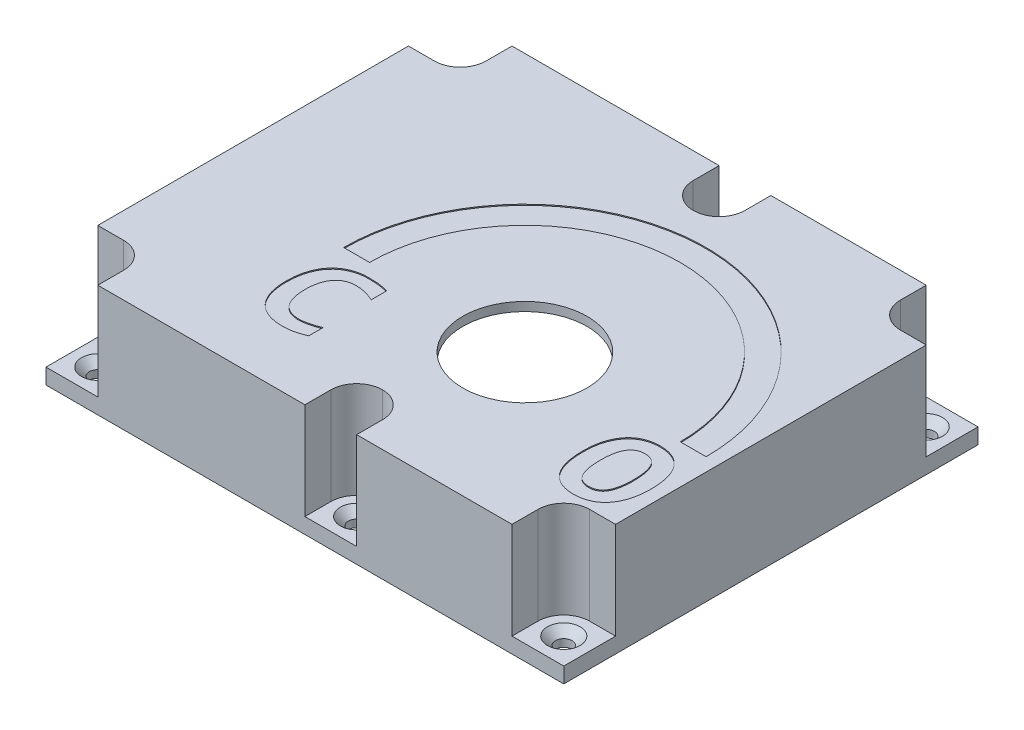
SolidWorks part; units mm, degrees
ref_plane "Płaszczyzna przednia" through (0, 0, 0) normal (0, 0, 1) x (1, 0, 0)
ref_plane "Płaszczyzna górna" through (0, 0, 0) normal (0, 1, 0) x (1, 0, 0)
ref_plane "Płaszczyzna prawa" through (0, 0, 0) normal (1, 0, 0) x (0, 0, -1)
sketch "Sketch1" plane through (0, 0, 0) normal (0, 1, 0) x (1, 0, 0)
  line L0 (-49.242, 28.8418) -> (-44.241, 28.8418)
  line L5 (-49.242, 38.8418) -> (0.758, 38.8418) construction
  line L18 (-49.242, 38.8418) -> (-49.242, -41.1582) construction
  line L19 (-49.242, -41.1582) -> (0.758, -41.1582) construction
  line L21 (50.758, 38.8418) -> (50.758, -41.1582) construction
  line L22 (-49.242, 38.8418) -> (-39.242, 38.8418) construction
  line L23 (-49.242, 38.8418) -> (-49.242, 28.8418) construction
  line L24 (-49.242, 28.8418) -> (-39.242, 28.8418) construction
  line L25 (-39.242, 38.8418) -> (-39.242, 28.8418) construction
  line L26 (50.758, 38.8418) -> (40.758, 38.8418) construction
  line L27 (50.758, 38.8418) -> (50.758, 28.8418) construction
  line L28 (50.758, 28.8418) -> (40.758, 28.8418) construction
  line L29 (40.758, 38.8418) -> (40.758, 28.8418) construction
  line L30 (50.758, -41.1582) -> (40.758, -41.1582) construction
  line L31 (50.758, -41.1582) -> (50.758, -31.1582) construction
  line L32 (50.758, -31.1582) -> (40.758, -31.1582) construction
  line L33 (40.758, -41.1582) -> (40.758, -31.1582) construction
  line L34 (-49.242, -41.1582) -> (-39.242, -41.1582) construction
  line L35 (-49.242, -41.1582) -> (-49.242, -31.1582) construction
  line L36 (-49.242, -31.1582) -> (-39.242, -31.1582) construction
  line L37 (-39.242, -41.1582) -> (-39.242, -31.1582) construction
  line L39 (0.758, 28.8418) -> (10.758, 28.8418) construction
  line L40 (0.758, 28.8418) -> (10.758, 28.8418) construction
  line L41 (0.758, 28.8418) -> (0.758, 38.8418) construction
  line L43 (10.758, 28.8418) -> (10.758, 38.8418) construction
  line L48 (0.758, -41.1582) -> (0.758, -31.1582) construction
  line L49 (0.758, -31.1582) -> (10.758, -31.1582) construction
  line L50 (10.758, -41.1582) -> (10.758, -31.1582) construction
  line L51 (-39.242, 33.8408) -> (-39.242, 38.8418)
  line L52 (0.758, 38.8418) -> (0.758, 33.8408)
  line L53 (5.757, 28.8418) -> (5.759, 28.8418)
  line L54 (10.758, 33.8408) -> (10.758, 38.8418)
  line L55 (40.758, 38.8418) -> (40.758, 33.8408)
  line L56 (45.757, 28.8418) -> (50.758, 28.8418)
  line L57 (50.758, -31.1582) -> (45.757, -31.1582)
  line L58 (40.758, -36.1572) -> (40.758, -41.1582)
  line L59 (10.758, -41.1582) -> (10.758, -36.1572)
  line L60 (5.759, -31.1582) -> (5.757, -31.1582)
  line L61 (0.758, -36.1572) -> (0.758, -41.1582)
  line L62 (-39.242, -41.1582) -> (-39.242, -36.1572)
  line L63 (-44.241, -31.1582) -> (-49.242, -31.1582)
  line L64 (-47.742, 27.3418) -> (-44.241, 27.3418)
  line L65 (-49.242, 38.8418) -> (-37.742, 38.8418) construction
  line L66 (-49.242, 38.8418) -> (-49.242, 27.3418) construction
  line L69 (-37.742, 33.8408) -> (-37.742, 37.3418)
  line L70 (-37.742, -39.6582) -> (-37.742, -36.1572)
  line L71 (-44.241, -29.6582) -> (-47.742, -29.6582)
  line L72 (39.258, 37.3418) -> (39.258, 33.8408)
  line L73 (45.757, 27.3418) -> (49.258, 27.3418)
  line L74 (39.258, -39.6582) -> (39.258, -36.1572)
  line L75 (45.757, -29.6582) -> (49.258, -29.6582)
  line L76 (-0.742, 37.3418) -> (-0.742, 33.8408)
  line L77 (5.757, 27.3418) -> (5.759, 27.3418)
  line L78 (12.258, 33.8408) -> (12.258, 37.3418)
  line L79 (-0.742, -39.6582) -> (-0.742, -36.1572)
  line L80 (5.757, -29.6582) -> (5.759, -29.6582)
  line L81 (12.258, -36.1572) -> (12.258, -39.6582)
  line L82 (-37.742, -39.6582) -> (-0.742, -39.6582)
  line L83 (-47.742, -29.6582) -> (-47.742, 27.3418)
  line L84 (-37.742, 37.3418) -> (-0.742, 37.3418)
  line L85 (49.258, -29.6582) -> (49.258, 27.3418)
  line L86 (10.758, -41.1582) -> (50.758, -41.1582) construction
  line L87 (12.258, 37.3418) -> (39.258, 37.3418)
  line L88 (-49.242, -31.1582) -> (-49.242, 28.8418)
  line L89 (12.258, -39.6582) -> (39.258, -39.6582)
  line L90 (10.758, 38.8418) -> (50.758, 38.8418) construction
  line L91 (-39.242, 38.8418) -> (0.758, 38.8418)
  line L92 (10.758, 38.8418) -> (40.758, 38.8418)
  line L93 (50.758, 28.8418) -> (50.758, -31.1582)
  line L94 (40.758, -41.1582) -> (10.758, -41.1582)
  line L95 (0.758, -41.1582) -> (-39.242, -41.1582)
  arc A0 (-39.242, -36.1572) -> (-44.241, -31.1582) centre (-44.241, -36.1572) ccw
  arc A1 (5.757, -31.1582) -> (0.758, -36.1572) centre (5.757, -36.1572) ccw
  arc A2 (10.758, -36.1572) -> (5.759, -31.1582) centre (5.759, -36.1572) ccw
  arc A3 (45.757, -31.1582) -> (40.758, -36.1572) centre (45.757, -36.1572) ccw
  arc A4 (40.758, 33.8408) -> (45.757, 28.8418) centre (45.757, 33.8408) ccw
  arc A5 (5.759, 28.8418) -> (10.758, 33.8408) centre (5.759, 33.8408) ccw
  arc A6 (0.758, 33.8408) -> (5.757, 28.8418) centre (5.757, 33.8408) ccw
  arc A7 (-44.241, 28.8418) -> (-39.242, 33.8408) centre (-44.241, 33.8408) ccw
  arc A8 (-37.742, -36.1572) -> (-44.241, -29.6582) centre (-44.241, -36.1572) ccw
  arc A9 (-0.742, -36.1572) -> (5.757, -29.6582) centre (5.757, -36.1572) cw
  arc A10 (5.759, -29.6582) -> (12.258, -36.1572) centre (5.759, -36.1572) cw
  arc A11 (39.258, -36.1572) -> (45.757, -29.6582) centre (45.757, -36.1572) cw
  arc A12 (39.258, 33.8408) -> (45.757, 27.3418) centre (45.757, 33.8408) ccw
  arc A13 (5.759, 27.3418) -> (12.258, 33.8408) centre (5.759, 33.8408) ccw
  arc A14 (-0.742, 33.8408) -> (5.757, 27.3418) centre (5.757, 33.8408) ccw
  arc A15 (-44.241, 27.3418) -> (-37.742, 33.8408) centre (-44.241, 33.8408) ccw
  point P53 (50.758, 27.3418)
  point P55 (39.258, 38.8418)
  point P61 (-0.742, 38.8418)
  point P81 (39.258, 27.3418)
  point P86 (-0.742, 27.3418)
  point P89 (-37.742, 27.3418)
  point P90 (-37.742, -39.6582)
  point P93 (-47.742, -29.6582)
  point P96 (-37.742, 37.3418)
  point P99 (49.258, -29.6582)
  dimension "D3" = 4.999
  dimension "D9" = 6.499
  dimension "D1" = 100
  dimension "D2" = 80
  dimension "D4" = 11.5
  dimension "D5" = 11.5
  dimension "D6" = 11.5
  dimension "D7" = 11.5
  dimension "D8" = 1.5
  dimension "D12" = 1.5
extrude "Boss-Extrude4" add sketch "Sketch1" along normal blind 20
sketch "Sketch2" plane through (0, 0, 0) normal (0, -1, 0) x (1, 0, 0)
  line L0 (0.758, 41.1582) -> (10.758, 41.1582) construction
  line L1 (-49.242, 31.1582) -> (-39.242, 31.1582) construction
  line L2 (-49.242, 31.1582) -> (-49.242, 41.1582) construction
  line L3 (-49.242, 41.1582) -> (-39.242, 41.1582) construction
  line L4 (-39.242, 31.1582) -> (-39.242, 41.1582) construction
  line L5 (40.758, 41.1582) -> (50.758, 41.1582) construction
  line L6 (40.758, 41.1582) -> (40.758, 31.1582) construction
  line L7 (40.758, 31.1582) -> (50.758, 31.1582) construction
  line L8 (50.758, 41.1582) -> (50.758, 31.1582) construction
  line L9 (-49.242, -28.8418) -> (-39.242, -28.8418) construction
  line L10 (-49.242, -28.8418) -> (-49.242, -38.8418) construction
  line L11 (-49.242, -38.8418) -> (-39.242, -38.8418) construction
  line L12 (-39.242, -28.8418) -> (-39.242, -38.8418) construction
  line L13 (50.758, -28.8418) -> (40.758, -28.8418) construction
  line L14 (50.758, -28.8418) -> (50.758, -38.8418) construction
  line L15 (50.758, -38.8418) -> (40.758, -38.8418) construction
  line L16 (40.758, -28.8418) -> (40.758, -38.8418) construction
  line L17 (0.758, 41.1582) -> (0.758, 31.1582) construction
  line L18 (10.758, 41.1582) -> (10.758, 31.1582) construction
  line L19 (0.758, 31.1582) -> (10.758, 31.1582) construction
  line L20 (0.758, -38.8418) -> (10.758, -38.8418) construction
  line L21 (0.758, -38.8418) -> (0.758, -28.8418) construction
  line L22 (10.758, -38.8418) -> (10.758, -28.8418) construction
  line L23 (0.758, -28.8418) -> (10.758, -28.8418) construction
  line L24 (0.758, -38.8418) -> (10.758, -38.8418)
  line L25 (-49.242, -38.8418) -> (-39.242, -38.8418)
  line L26 (-49.242, -38.8418) -> (-49.242, -28.8418)
  line L27 (-49.242, -28.8418) -> (-44.241, -28.8418)
  line L28 (-39.242, -38.8418) -> (-39.242, -33.8408)
  line L29 (-49.242, 41.1582) -> (-39.242, 41.1582)
  line L30 (-49.242, 41.1582) -> (-49.242, 31.1582)
  line L31 (-49.242, 31.1582) -> (-44.241, 31.1582)
  line L32 (-39.242, 41.1582) -> (-39.242, 36.1572)
  line L33 (50.758, 41.1582) -> (40.758, 41.1582)
  line L34 (50.758, 41.1582) -> (50.758, 31.1582)
  line L35 (50.758, 31.1582) -> (45.757, 31.1582)
  line L36 (40.758, 41.1582) -> (40.758, 36.1572)
  line L37 (50.758, -38.8418) -> (40.758, -38.8418)
  line L38 (50.758, -38.8418) -> (50.758, -28.8418)
  line L39 (50.758, -28.8418) -> (45.757, -28.8418)
  line L40 (40.758, -38.8418) -> (40.758, -33.8408)
  line L41 (10.758, -38.8418) -> (10.758, -33.8408)
  line L42 (5.759, -28.8418) -> (5.757, -28.8418)
  line L43 (0.758, -33.8408) -> (0.758, -38.8418)
  line L44 (0.758, 41.1582) -> (10.758, 41.1582)
  line L45 (10.758, 41.1582) -> (10.758, 36.1572)
  line L46 (5.759, 31.1582) -> (5.757, 31.1582)
  line L47 (0.758, 36.1572) -> (0.758, 41.1582)
  arc A0 (-44.241, -28.8418) -> (-39.242, -33.8408) centre (-44.241, -33.8408) cw
  arc A1 (45.757, 31.1582) -> (40.758, 36.1572) centre (45.757, 36.1572) cw
  arc A2 (45.757, -28.8418) -> (40.758, -33.8408) centre (45.757, -33.8408) ccw
  arc A3 (5.757, -28.8418) -> (0.758, -33.8408) centre (5.757, -33.8408) ccw
  arc A4 (10.758, -33.8408) -> (5.759, -28.8418) centre (5.759, -33.8408) ccw
  arc A5 (10.758, 36.1572) -> (5.759, 31.1582) centre (5.759, 36.1572) cw
  arc A6 (5.757, 31.1582) -> (0.758, 36.1572) centre (5.757, 36.1572) cw
  arc A7 (-44.241, 31.1582) -> (-39.242, 36.1572) centre (-44.241, 36.1572) ccw
  dimension "D1" = 4.999
extrude "Boss-Extrude5" add sketch "Sketch2" against normal blind 3
sketch "Sketch3" plane through (0, 20, 0) normal (0, 1, 0) x (1, 0, 0)
  line L0 (0.758, -41.1582) -> (0.758, -36.1572)
  line L1 (-49.242, 38.8418) -> (50.758, 38.8418) construction
  line L2 (-49.242, 38.8418) -> (-49.242, -41.1582) construction
  line L3 (-49.242, -41.1582) -> (50.758, -41.1582) construction
  line L4 (50.758, 38.8418) -> (50.758, -41.1582) construction
  line L5 (-49.242, 38.8418) -> (-39.242, 38.8418)
  line L6 (-49.242, 38.8418) -> (-49.242, 28.8418)
  line L7 (-49.242, 28.8418) -> (-44.241, 28.8418)
  line L8 (-39.242, 38.8418) -> (-39.242, 33.8408)
  line L9 (50.758, 38.8418) -> (40.758, 38.8418)
  line L10 (50.758, 38.8418) -> (50.758, 28.8418)
  line L11 (50.758, 28.8418) -> (45.757, 28.8418)
  line L12 (40.758, 38.8418) -> (40.758, 33.8408)
  line L13 (50.758, -41.1582) -> (40.758, -41.1582)
  line L14 (50.758, -41.1582) -> (50.758, -31.1582)
  line L15 (50.758, -31.1582) -> (45.757, -31.1582)
  line L16 (40.758, -41.1582) -> (40.758, -36.1572)
  line L17 (-49.242, -41.1582) -> (-39.242, -41.1582)
  line L18 (-49.242, -41.1582) -> (-49.242, -31.1582)
  line L19 (-49.242, -31.1582) -> (-44.241, -31.1582)
  line L20 (-39.242, -41.1582) -> (-39.242, -36.1572)
  line L21 (10.758, -41.1582) -> (10.758, -36.1572)
  line L22 (5.759, -31.1582) -> (5.757, -31.1582)
  line L23 (0.758, 38.8418) -> (0.758, 33.8408)
  line L24 (5.757, 28.8418) -> (5.759, 28.8418)
  line L25 (10.758, 33.8408) -> (10.758, 38.8418)
  line L26 (-49.242, -31.1582) -> (-49.242, 28.8418)
  line L27 (-39.242, 38.8418) -> (0.758, 38.8418)
  line L28 (10.758, 38.8418) -> (40.758, 38.8418)
  line L29 (50.758, 28.8418) -> (50.758, -31.1582)
  line L30 (40.758, -41.1582) -> (10.758, -41.1582)
  line L31 (0.758, -41.1582) -> (-39.242, -41.1582)
  arc A0 (45.757, 28.8418) -> (40.758, 33.8408) centre (45.757, 33.8408) cw
  arc A1 (-44.241, 28.8418) -> (-39.242, 33.8408) centre (-44.241, 33.8408) ccw
  arc A2 (-44.241, -31.1582) -> (-39.242, -36.1572) centre (-44.241, -36.1572) cw
  arc A3 (45.757, -31.1582) -> (40.758, -36.1572) centre (45.757, -36.1572) ccw
  arc A4 (10.758, -36.1572) -> (5.759, -31.1582) centre (5.759, -36.1572) ccw
  arc A5 (0.758, -36.1572) -> (5.757, -31.1582) centre (5.757, -36.1572) cw
  arc A6 (5.759, 28.8418) -> (10.758, 33.8408) centre (5.759, 33.8408) ccw
  arc A7 (0.758, 33.8408) -> (5.757, 28.8418) centre (5.757, 33.8408) ccw
  dimension "D1" = 4.999
extrude "Boss-Extrude6" add sketch "Sketch3" along normal blind 1.7 contours A7 L23 L27 L8 A1 L7 L26 L19 A2 L20 L31 L0 A5 L22 A4 L21 L30 L16 A3 L15 L29 L11 A0 L12 L28 L25 A6 L24 region at (0.6381, 20, 1.1582)
sketch "Sketch6" plane through (0, 3, 0) normal (0, 1, 0) x (1, 0, 0)
  point P0 (-44.241, 33.8408)
  point P3 (45.757, 33.8408)
  point P6 (45.757, -36.1572)
  point P9 (-44.241, -36.1572)
  point P12 (5.757, -36.1572)
  point P15 (5.757, 33.8408)
hole_wizard "CSK for M3 Countersunk Flat Head Screw1" positions "Sketch6" profile "Sketch5" countersink size "M3" standard "ISO" end condition through all
sketch "Sketch5" plane through (-44.241, 3, -33.8408) normal (1, 0, 0) x (0, 0, 1)
  line L0 (0, 0) -> (0, 3)
  line L1 (0, 3) -> (1.6, 3)
  line L2 (1.6, 3) -> (1.6, 1.55)
  line L3 (1.6, 1.55) -> (3.15, 0)
  line L5 (3.15, 0) -> (0, 0)
  line L6 (-1.6, 1.55) -> (-3.15, 0) construction
  line L11 (0, -6.35) -> (0, 107.95) construction
  dimension "Thru Hole Dia." = 3.2
  dimension "Thru Hole Depth" = 3
  dimension "Near C'Sink Dia." = 6.3
  dimension "Near C'Sink Angle" = 90
sketch "Sketch7" plane through (0, 21.7, 0) normal (0, 1, 0) x (1, 0, 0)
  line L0 (50.758, 28.8418) -> (50.758, -31.1582) construction
  line L1 (40.758, -41.1582) -> (10.758, -41.1582) construction
  circle A0 centre (13.1964, -11.1082) radius 12
  point P0 (13.1964, -11.1082)
  dimension "D1" = 37.5616
  dimension "D2" = 30.05
extrude "Cut-Extrude1" cut sketch "Sketch7" against normal through all
sketch "Sketch8" plane through (0, 21.7, 0) normal (0, 1, 0) x (1, 0, 0)
  line L0 (-21.8036, -11.1082) -> (-16.8036, -11.1082)
  line L1 (13.1964, -11.1082) -> (-16.8036, -11.1082) construction
  line L4 (43.1964, -11.1082) -> (48.1964, -11.1082)
  arc A1 (-21.8036, -11.1082) -> (48.1964, -11.1082) centre (13.1964, -11.1082) cw
  arc A2 (-16.8036, -11.1082) -> (43.1964, -11.1082) centre (13.1964, -11.1082) cw
  text T0 "<b>C</b>" font "Consolas" height 16
  text T1 "O" font "Consolas" height 16
  point P5 (-21.8036, -11.1082)
  point P9 (0, 0)
  point P10 (-26.1685, -33.1201)
  point P11 (0, 0)
  point P12 (-24.8548, -31.2174)
  point P13 (-21.8036, -32.3473)
  point P14 (33.8755, -31.7291)
  point P15 (33.7209, -32.8882)
  point P16 (-21.8036, -29.5653)
  point P17 (-22.4592, -29.6426)
  point P18 (0, 0)
  point P19 (0, 0)
  point P20 (-23.7729, -29.9517)
  point P21 (-23.3866, -29.9517)
  point P22 (-22.8456, -29.9517)
  point P23 (-22.6864, -29.9555)
  point P24 (33.1442, -29.9555)
  point P25 (34.8389, -29.9555)
  dimension "D1" = 30
  dimension "D3" = 35
extrude "Cut-Extrude2" cut sketch "Sketch8" against normal blind 0.2
